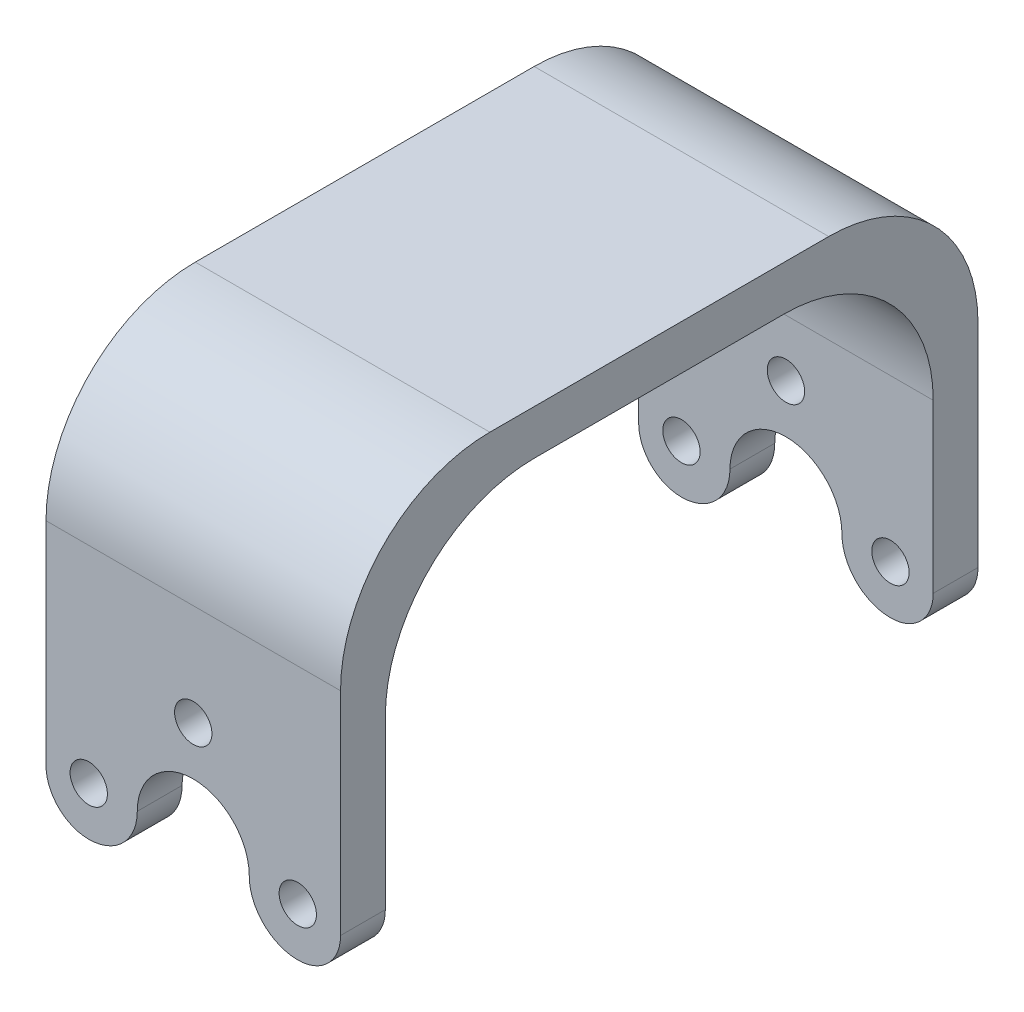
SolidWorks part; units mm, degrees
ref_plane "Front Plane" through (0, 0, 0) normal (1, 0, 0) x (0, 1, 0)
ref_plane "Top Plane" through (0, 0, 0) normal (0, 0, 1) x (0, 1, 0)
ref_plane "Right Plane" through (0, 0, 0) normal (0, 1, 0) x (-1, 0, 0)
sketch "Sketch2" plane through (0, 0, 0) normal (0, 0, 1) x (0, 1, 0)
  line L1 (-201.4286, 287.5871) -> (-181.4286, 287.5871)
  line L2 (-201.4286, 287.5871) -> (-201.4286, 267.8571)
  line L3 (-201.4286, 267.8571) -> (-181.4286, 267.8571)
  line L4 (-181.4286, 287.5871) -> (-181.4286, 267.8571)
  line L5 (-181.4286, 287.5871) -> (-167.4286, 287.5871)
  line L6 (-181.4286, 287.5871) -> (-181.4286, 267.8571)
  line L7 (-181.4286, 267.8571) -> (-167.4286, 267.8571)
  line L8 (-167.4286, 287.5871) -> (-167.4286, 267.8571)
  dimension "D1" = 19.73
  dimension "D2" = 20
  dimension "D3" = 14
extrude "Boss-Extrude1" add sketch "Sketch2" along normal blind 42.7 contours L8 L5 L4 L7 | L1 L2 L3 L4 region at (-277.7221, -174.4286, 0)
sketch "Sketch3" plane through (0, -201.4286, 0) normal (0, -1, 0) x (1, 0, 0)
  line L0 (-287.5871, 42.7) -> (-287.5871, 0) construction
  line L1 (-287.5871, 39.7) -> (-267.8571, 39.7)
  line L2 (-287.5871, 39.7) -> (-287.5871, 3)
  line L3 (-287.5871, 3) -> (-267.8571, 3)
  line L4 (-267.8571, 39.7) -> (-267.8571, 3)
  line L5 (-267.8571, 42.7) -> (-267.8571, 0) construction
  line L6 (-287.5871, 0) -> (-267.8571, 0) construction
  line L7 (-287.5871, 42.7) -> (-267.8571, 42.7) construction
  dimension "D1" = 3
  dimension "D2" = 3
extrude "Cut-Extrude1" cut sketch "Sketch3" against normal offset from surface (31 mm away) 3 up to face at (-277.7221, -167.4286, 21.35)
fillet "Fillet1" radius 10 4 edges at (-277.7221, -167.4286, 42.7) (-277.7221, -167.4286, 0) (-277.7221, -170.4286, 39.7) (-277.7221, -170.4286, 3)
sketch "Sketch4" plane through (0, 0, 0) normal (0, 0, -1) x (1, 0, 0)
  line L0 (-277.7221, 167.4286) -> (-277.7221, 201.4286) construction
  line L1 (-267.8571, 167.4286) -> (-287.5871, 167.4286) construction
  line L2 (-287.5871, 201.4286) -> (-267.8571, 201.4286) construction
  line L3 (-284.7225, 191.2286) -> (-277.7221, 198.2289) construction
  line L4 (-277.7221, 198.2289) -> (-270.7218, 191.2286) construction
  line L5 (-270.7218, 191.2286) -> (-277.7221, 184.2282) construction
  line L6 (-277.7221, 184.2282) -> (-284.7225, 191.2286) construction
  line L7 (-287.5871, 194.4786) -> (-284.7225, 194.4786)
  line L8 (-287.5871, 201.4286) -> (-287.5871, 177.4286) construction
  line L9 (-267.8571, 194.4786) -> (-270.7218, 194.4786)
  circle A0 centre (-277.7221, 191.2286) radius 7.0004
  circle A1 centre (-277.7221, 198.2289) radius 1.25
  circle A2 centre (-270.7218, 191.2286) radius 1.25
  circle A3 centre (-284.7225, 191.2286) radius 1.25
  circle A8 centre (-277.7221, 184.2282) radius 1.25
  arc A9 (-284.7225, 194.4786) -> (-281.4725, 191.2286) centre (-284.7225, 191.2286) cw
  arc A10 (-281.4725, 191.2286) -> (-273.9718, 191.2286) centre (-277.7221, 191.2286) ccw
  circle A11 centre (-277.7221, 191.2286) radius 0.05
  arc A12 (-270.7218, 194.4786) -> (-273.9718, 191.2286) centre (-270.7218, 191.2286) ccw
  line M1 (-287.5871, 201.4286) -> (-287.5871, 177.4286)
  line M3 (-267.8571, 177.4286) -> (-267.8571, 201.4286)
  line M4 (-267.8571, 201.4286) -> (-287.5871, 201.4286)
  dimension "D1" = 10.2
  dimension "D2" = 2.5
  dimension "D4" = 0.1
  dimension "D5" = 2
  dimension "D3" = 9.9
extrude "Cut-Extrude2" cut sketch "Sketch4" against normal through all contours A0 A3 | A0 A3 | A0 A2 | A0 A2 | A0 A8 | A0 A8 | A12 L9 L7 A9 A0 A1 M3 M4 M1 | A12 A0 A1 A9 A10 A11 | A0 A1 | A0 A1 | A11 region at (-287.3777, -197.9536, 0) region at (-277.7221, -193.1784, 0) region at (-277.7221, -198.7388, 0) region at (-277.7221, -197.6788, 0) region at (-284.1724, -191.2286, 0) region at (-285.2324, -191.2286, 0) region at (-277.7221, -184.7783, 0) region at (-277.7221, -183.7183, 0) region at (-270.2119, -191.2286, 0) region at (-271.2719, -191.2286, 0)
fillet "Fillet2" radius 2.85 4 edges at (-267.8571, -194.4786, 41.2) (-287.5871, -194.4786, 41.2) (-267.8571, -194.4786, 1.5) (-287.5871, -194.4786, 1.5)
